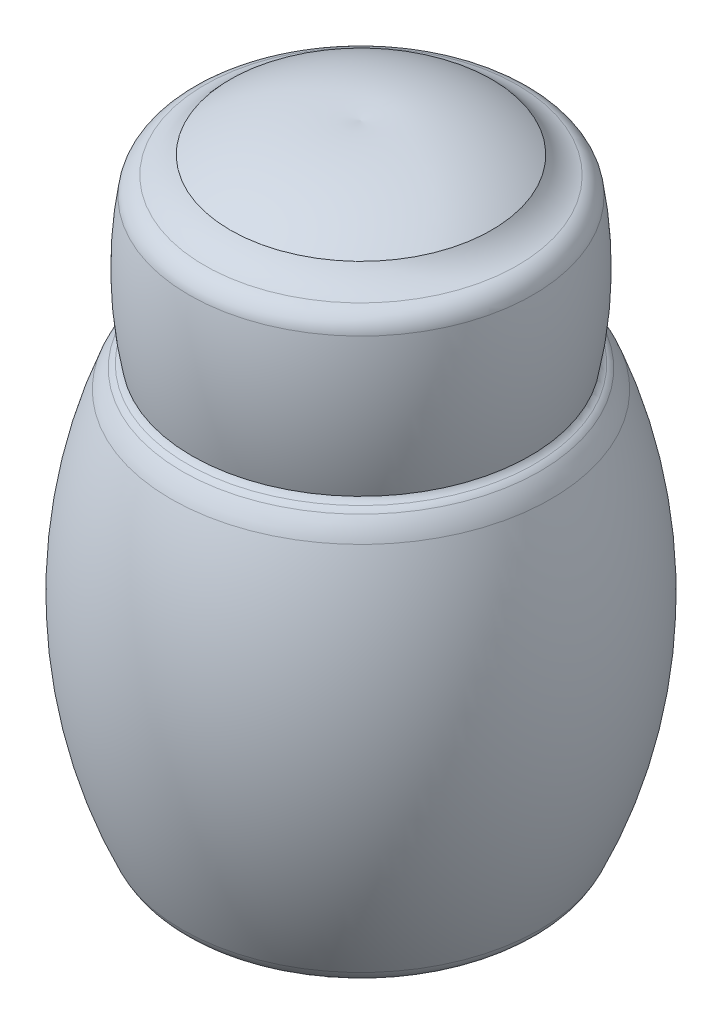
SolidWorks part; units mm, degrees
ref_plane "Front Plane" through (0, 0, 0) normal (0, 0, 1) x (1, 0, 0)
ref_plane "Top Plane" through (0, 0, 0) normal (0, 1, 0) x (1, 0, 0)
ref_plane "Right Plane" through (0, 0, 0) normal (1, 0, 0) x (0, 0, -1)
sketch "Sketch2" plane through (0, 0, 0) normal (0, 0, 1) x (1, 0, 0)
  line L0 (0, 300) -> (0, -290) construction
  line L1 (-142.8245, 0) -> (143.6743, 0) construction
  line L2 (-202.362, 110.7345) -> (365.1962, 110.7345) construction
  line L3 (0, -20) -> (-90, -20) construction
  line L4 (-90, -83.4454) -> (-90, 331.1943) construction
  line L8 (-20.6932, 220) -> (-90, 220)
  line L9 (-20.6932, 205) -> (-90, 205)
  line L10 (-90, 220) -> (-90, 205)
  line L11 (-4.9262, 0) -> (-19.2818, 0)
  line L12 (-19.2818, 0) -> (-19.2818, 12.4799)
  line L13 (-19.2818, 12.4799) -> (-12.1346, 13.1544)
  line L14 (-3.4461, 214.5466) -> (-3.4461, 294.5466) construction
  line L15 (-90, 320) -> (0, 320) construction
  line L16 (-88.8438, 310.0671) -> (-90, 310.0671)
  line L17 (-90, 310.0671) -> (-90, 320)
  arc A0 (1.5112, 6.9259) -> (7.2919, 200.8089) centre (-225.9175, 110.7345) ccw
  arc A2 (1.5112, 6.9259) -> (-4.9262, 0) centre (-12.1346, 13.1544) cw
  arc A10 (-12.1346, 13.1544) -> (-12.1346, 13.1544) centre (-12.1346, 13.1544) cw
  arc A11 (-12.1346, 13.1544) -> (-6.7007, 195.4045) centre (-225.9175, 110.7345) ccw
  arc A12 (-20.6932, 205) -> (-6.7007, 195.4045) centre (-20.6932, 190) cw
  arc A13 (-9.9043, 295.7368) -> (-23.0961, 304.8325) centre (-1.798, 321.6077) cw
  arc A14 (-23.0961, 304.8325) -> (-90, 320) centre (-78.0678, 217.4928) ccw
  arc A15 (-1.9915, 286.6063) -> (-3.4461, 214.5466) centre (-199.4053, 254.5466) cw
  arc A16 (-1.9915, 286.6063) -> (-9.9043, 295.7368) centre (-13.3428, 284.7628) ccw
  arc A17 (1.5294, 210.1533) -> (7.2919, 200.8089) centre (-20.6932, 190) cw
  arc A18 (-20.6932, 220) -> (-3.4461, 214.5466) centre (-20.6932, 190) cw
  arc A19 (-3.4461, 214.5466) -> (-1.0214, 212.1769) centre (2.1016, 217.7977) ccw
  arc A20 (-20.6932, 220) -> (7.2919, 200.8089) centre (-20.6932, 190) cw construction
  arc A21 (1.5294, 210.1533) -> (-1.0214, 212.1769) centre (-5.8781, 203.4355) ccw
  arc A22 (-11.8622, 285.0033) -> (-13.244, 216.5466) centre (-199.4053, 254.5466) cw
  arc A23 (-11.8622, 285.0033) -> (-12.8943, 286.1942) centre (-13.3428, 284.7628) ccw
  arc A24 (-12.8943, 286.1942) -> (-29.7371, 297.1814) centre (-1.798, 321.6077) cw
  arc A25 (-29.7371, 297.1814) -> (-88.8438, 310.0671) centre (-78.0678, 217.4928) ccw
  point P11 (-86.4792, 156.5384)
  point P13 (-4.944, -0.0828)
  point P14 (0, 0)
  point P30 (-6.5748, 7.2962)
  point P31 (-86.4792, 156.5384)
  point P32 (-89.8547, -12.7145)
  point P50 (0, 211.7207)
  point P60 (-20.6932, 303.1525)
  point P62 (-23.0961, 304.8325)
  dimension "D3" = 250
  dimension "D6" = 15
  dimension "D7" = 15
  dimension "D1" = 30
  dimension "D4" = 220
  dimension "D10" = 200
  dimension "D11" = 11.5
  dimension "D12" = 10
  dimension "D2" = 90
  dimension "D5" = 20
  dimension "D8" = 100
  dimension "D9" = 80
  dimension "D13" = 10
revolve "Revolve1" add sketch "Sketch2" angle 360 about L4 region at (-17.0273, 217.2766, 0)
sketch "Sketch3" plane through (0, 0, 0) normal (0, -1, 0) x (1, 0, 0)
  circle A0 centre (-90, 0) radius 77.5012
  circle A1 centre (-90, 0) radius 81
  dimension "D1" = 155.0025
  dimension "D2" = 162
extrude "Cut-Extrude1" cut sketch "Sketch3" against normal blind 20
revolve "Revolve2" add sketch "Sketch2<3>" angle 360 about L4 region at (-8.0279, 251.9103, 0)
sketch "Sketch2<3>" plane through (0, 0, 0) normal (0, 0, 1) x (1, 0, 0) same geometry as "Sketch2"
